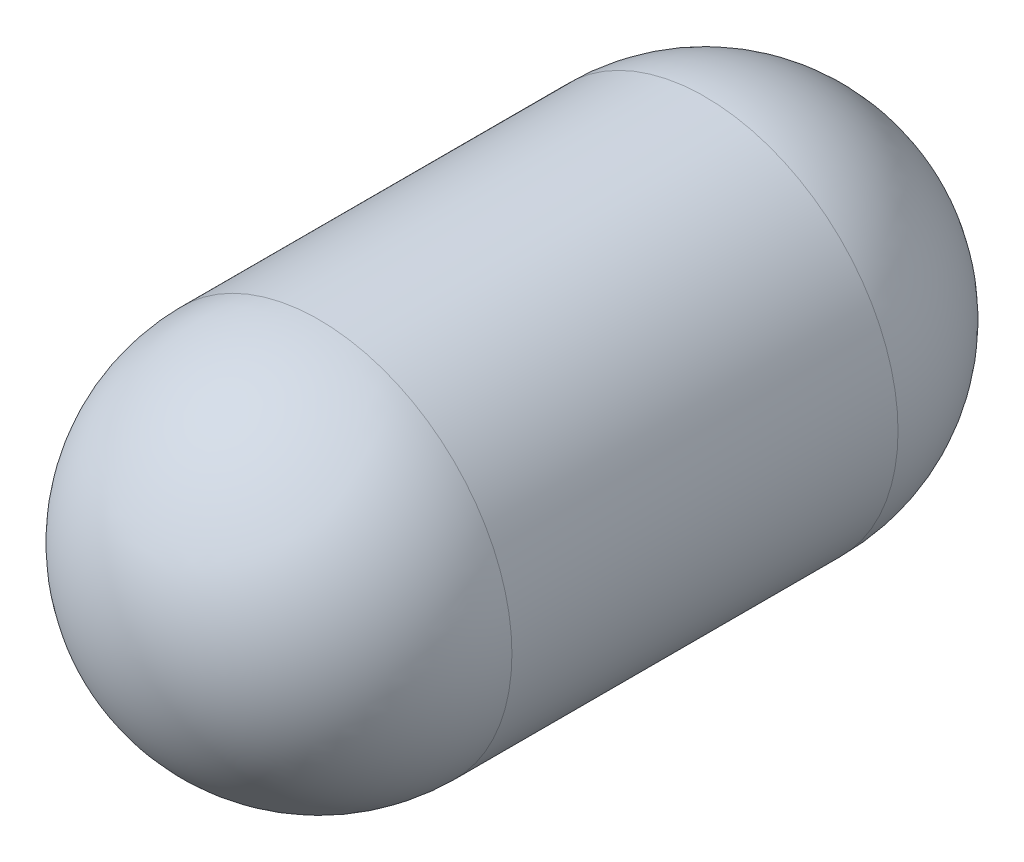
SolidWorks part; units mm, degrees
ref_plane "Front Plane" through (0, 0, 0) normal (0, 0, 1) x (1, 0, 0)
ref_plane "Top Plane" through (0, 0, 0) normal (0, 1, 0) x (1, 0, 0)
ref_plane "Right Plane" through (0, 0, 0) normal (1, 0, 0) x (0, 0, -1)
sketch "Sketch1" plane through (0, 0, 0) normal (0, 0, 1) x (1, 0, 0)
  circle A0 centre (0, 0) radius 0.5
  point P2 (0, 0)
  point P3 (0, 0)
  dimension "D1" = 1
extrude "Boss-Extrude1" add sketch "Sketch1" along normal blind 0.5 and the other way blind 0.5
dome "Dome1" faces to dome 1 distance 0.5 reverse direction no elliptical dome no face at (0.5, 0, 0.5) parameters "D1"=0.5
dome "Dome2" faces to dome 1 distance 0.5 reverse direction no elliptical dome no face at (0.5, 0, -0.5) parameters "D1"=0.5
